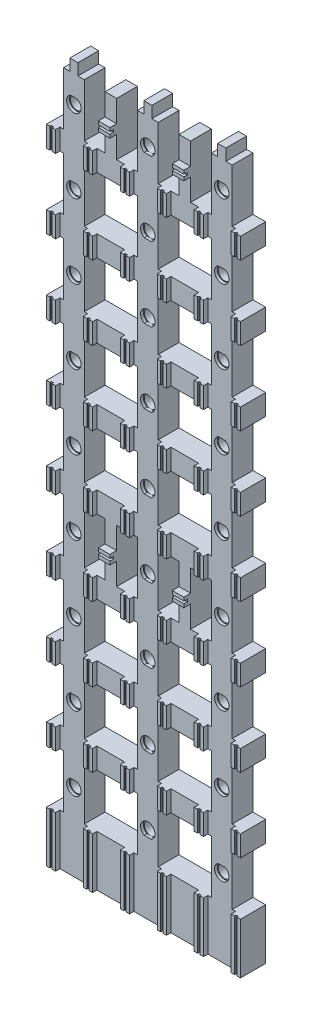
SolidWorks part; units mm, degrees
ref_plane "Front Plane" through (0, 0, 0) normal (0, 0, 1) x (1, 0, 0)
ref_plane "Top Plane" through (0, 0, 0) normal (0, 1, 0) x (1, 0, 0)
ref_plane "Right Plane" through (0, 0, 0) normal (1, 0, 0) x (0, 0, -1)
sketch "Sketch1" plane through (0, 0, 0) normal (0, 0, 1) x (1, 0, 0)
  line L1 (42, -11) -> (-42, -11)
  line L2 (42, -11) -> (42, 11)
  line L3 (42, 11) -> (-42, 11)
  line L4 (-42, -11) -> (-42, 11)
  line L5 (42, -11) -> (-42, 11) construction
  line L6 (42, 11) -> (-42, -11) construction
  point P0 (0, 0)
  dimension "D1" = 22
  dimension "D2" = 84
extrude "Boss-Extrude1" add sketch "Sketch1" along normal blind 9
sketch "Sketch2" plane through (0, 0, 9) normal (0, 0, 1) x (1, 0, 0)
  line L0 (42, 11) -> (-42, 11) construction
  line L1 (-36.5, 11) -> (-27.5, 11)
  line L2 (-36.5, 11) -> (-36.5, 295) construction
  line L3 (-36.5, 295) -> (-27.5, 295) construction
  line L4 (-27.5, 11) -> (-27.5, 295) construction
  line L5 (-42, 11) -> (-42, -11) construction
  line L6 (-33.75, 295) -> (-30.25, 295)
  line L7 (-30.25, 295) -> (-30.25, 290)
  line L8 (-30.25, 290) -> (-27.5, 290)
  line L9 (-27.5, 290) -> (-27.5, 11)
  line L10 (-36.5, 11) -> (-36.5, 290)
  line L11 (-36.5, 290) -> (-33.75, 290)
  line L12 (-33.75, 290) -> (-33.75, 295)
  point P10 (-32, 295)
  point P15 (-32, 11)
  dimension "D1" = 5.5
  dimension "D2" = 9
  dimension "D3" = 284
  dimension "D4" = 5
  dimension "D5" = 3.5
extrude "Boss-Extrude2" add sketch "Sketch2" against normal up to surface (9 mm away) up to face at (0, 0, 0)
pattern_linear "LPattern1" count 3 spacing 32 along (1, 0, 0) of "Boss-Extrude2"
sketch "Sketch3" plane through (0, 0, 9) normal (0, 0, 1) x (1, 0, 0)
  line L0 (-42, 11) -> (-42, -11) construction
  line L1 (-42, 43) -> (42, 43)
  line L2 (-42, 43) -> (-42, 34)
  line L3 (-42, 34) -> (42, 34)
  line L4 (42, 43) -> (42, 34)
  line L5 (42, -11) -> (42, 11) construction
  line L6 (-36.5, 11) -> (-42, 11) construction
  dimension "D1" = 23
  dimension "D2" = 9
extrude "Boss-Extrude3" add sketch "Sketch3" against normal up to surface (9 mm away) up to face at (0, 189.8571, 0)
pattern_linear "LPattern2" count 8 spacing 32 along (0, 1, 0) of "Boss-Extrude3"
sketch "Sketch4" plane through (0, 0, 9) normal (0, 0, 1) x (1, 0, 0)
  line L0 (-27.5, 130) -> (-4.5, 130) construction
  line L1 (-13.5, 130) -> (-18.5, 130)
  line L2 (-13.5, 130) -> (-13.5, 107)
  line L3 (-13.5, 107) -> (-18.5, 107)
  line L4 (-18.5, 130) -> (-18.5, 107)
  line L5 (-4.5, 107) -> (-27.5, 107) construction
  point P8 (-16, 107)
  dimension "D1" = 5
extrude "Boss-Extrude4" add sketch "Sketch4" against normal up to surface (9 mm away) up to face at (-16, 246.5, 0)
pattern_linear "LPattern3" count 2 spacing 32 along (1, 0, 0) count 2 spacing 160 along (0, 1, 0) of "Boss-Extrude4"
sketch "Sketch5" plane through (0, 0, 9) normal (0, 0, 1) x (1, 0, 0)
  line L0 (-36.5, 22.5) -> (-27.5, 22.5) construction
  line L1 (-36.5, 34) -> (-36.5, 11) construction
  line L2 (-27.5, 11) -> (-27.5, 34) construction
  line L3 (-4.5, 22.5) -> (4.5, 22.5) construction
  line L4 (-4.5, 34) -> (-4.5, 11) construction
  line L5 (4.5, 11) -> (4.5, 34) construction
  line L6 (27.5, 22.5) -> (36.5, 22.5) construction
  line L7 (27.5, 34) -> (27.5, 11) construction
  line L8 (36.5, 11) -> (36.5, 34) construction
  circle A0 centre (-32, 22.5) radius 2.725
  circle A1 centre (0, 22.5) radius 2.725
  circle A2 centre (32, 22.5) radius 2.725
  circle A3 centre (-32, 54.5) radius 2.725
  circle A4 centre (0, 54.5) radius 2.725
  circle A5 centre (32, 54.5) radius 2.725
  circle A6 centre (-32, 86.5) radius 2.725
  circle A7 centre (0, 86.5) radius 2.725
  circle A8 centre (32, 86.5) radius 2.725
  circle A9 centre (-32, 118.5) radius 2.725
  circle A10 centre (0, 118.5) radius 2.725
  circle A11 centre (32, 118.5) radius 2.725
  circle A12 centre (-32, 150.5) radius 2.725
  circle A13 centre (0, 150.5) radius 2.725
  circle A14 centre (32, 150.5) radius 2.725
  circle A15 centre (-32, 182.5) radius 2.725
  circle A16 centre (0, 182.5) radius 2.725
  circle A17 centre (32, 182.5) radius 2.725
  circle A18 centre (-32, 214.5) radius 2.725
  circle A19 centre (0, 214.5) radius 2.725
  circle A20 centre (32, 214.5) radius 2.725
  circle A21 centre (-32, 246.5) radius 2.725
  circle A22 centre (0, 246.5) radius 2.725
  circle A23 centre (32, 246.5) radius 2.725
  circle A24 centre (-32, 278.5) radius 2.725
  circle A25 centre (0, 278.5) radius 2.725
  circle A26 centre (32, 278.5) radius 2.725
  dimension "D1" = 5.45
  dimension "D3" = 32
  dimension "D2" = 9
extrude "Cut-Extrude1" cut sketch "Sketch5" against normal through all
sketch "Sketch6" plane through (0, 0, 9) normal (0, 0, 1) x (1, 0, 0)
  line L27 (-33.5297, 25.225) -> (-30.4703, 25.225)
  line L28 (-1.5297, 19.775) -> (1.5297, 19.775)
  line L29 (30.4703, 25.225) -> (33.5297, 25.225)
  line L30 (-33.5297, 57.225) -> (-30.4703, 57.225)
  line L31 (-1.5297, 51.775) -> (1.5297, 51.775)
  line L32 (30.4703, 57.225) -> (33.5297, 57.225)
  line L33 (-33.5297, 89.225) -> (-30.4703, 89.225)
  line L34 (-1.5297, 83.775) -> (1.5297, 83.775)
  line L35 (30.4703, 89.225) -> (33.5297, 89.225)
  line L36 (-33.5297, 121.225) -> (-30.4703, 121.225)
  line L37 (-1.5297, 115.775) -> (1.5297, 115.775)
  line L38 (30.4703, 121.225) -> (33.5297, 121.225)
  line L39 (-33.5297, 153.225) -> (-30.4703, 153.225)
  line L40 (-1.5297, 147.775) -> (1.5297, 147.775)
  line L41 (30.4703, 153.225) -> (33.5297, 153.225)
  line L42 (-33.5297, 185.225) -> (-30.4703, 185.225)
  line L43 (-1.5297, 179.775) -> (1.5297, 179.775)
  line L44 (30.4703, 185.225) -> (33.5297, 185.225)
  line L45 (-33.5297, 217.225) -> (-30.4703, 217.225)
  line L46 (-1.5297, 211.775) -> (1.5297, 211.775)
  line L47 (30.4703, 217.225) -> (33.5297, 217.225)
  line L48 (-33.5297, 249.225) -> (-30.4703, 249.225)
  line L49 (-1.5297, 243.775) -> (1.5297, 243.775)
  line L50 (30.4703, 249.225) -> (33.5297, 249.225)
  line L51 (-33.5297, 281.225) -> (-30.4703, 281.225)
  line L52 (-1.5297, 275.775) -> (1.5297, 275.775)
  line L53 (30.4703, 281.225) -> (33.5297, 281.225)
  arc A30 (-33.5297, 25.225) -> (-30.4703, 25.225) centre (-32, 22.5) ccw
  arc A31 (1.5297, 19.775) -> (-1.5297, 19.775) centre (0, 22.5) ccw
  arc A32 (30.4703, 25.225) -> (33.5297, 25.225) centre (32, 22.5) ccw
  circle A33 centre (32, 22.5) radius 2.725 construction
  circle A34 centre (0, 22.5) radius 2.725 construction
  circle A35 centre (-32, 22.5) radius 2.725 construction
  arc A36 (-33.5297, 57.225) -> (-30.4703, 57.225) centre (-32, 54.5) ccw
  arc A37 (1.5297, 51.775) -> (-1.5297, 51.775) centre (0, 54.5) ccw
  arc A38 (30.4703, 57.225) -> (33.5297, 57.225) centre (32, 54.5) ccw
  arc A39 (-33.5297, 89.225) -> (-30.4703, 89.225) centre (-32, 86.5) ccw
  arc A40 (1.5297, 83.775) -> (-1.5297, 83.775) centre (0, 86.5) ccw
  arc A41 (30.4703, 89.225) -> (33.5297, 89.225) centre (32, 86.5) ccw
  arc A42 (-33.5297, 121.225) -> (-30.4703, 121.225) centre (-32, 118.5) ccw
  arc A43 (1.5297, 115.775) -> (-1.5297, 115.775) centre (0, 118.5) ccw
  arc A44 (30.4703, 121.225) -> (33.5297, 121.225) centre (32, 118.5) ccw
  arc A45 (-33.5297, 153.225) -> (-30.4703, 153.225) centre (-32, 150.5) ccw
  arc A46 (1.5297, 147.775) -> (-1.5297, 147.775) centre (0, 150.5) ccw
  arc A47 (30.4703, 153.225) -> (33.5297, 153.225) centre (32, 150.5) ccw
  arc A48 (-33.5297, 185.225) -> (-30.4703, 185.225) centre (-32, 182.5) ccw
  arc A49 (1.5297, 179.775) -> (-1.5297, 179.775) centre (0, 182.5) ccw
  arc A50 (30.4703, 185.225) -> (33.5297, 185.225) centre (32, 182.5) ccw
  arc A51 (-33.5297, 217.225) -> (-30.4703, 217.225) centre (-32, 214.5) ccw
  arc A52 (1.5297, 211.775) -> (-1.5297, 211.775) centre (0, 214.5) ccw
  arc A53 (30.4703, 217.225) -> (33.5297, 217.225) centre (32, 214.5) ccw
  arc A54 (-33.5297, 249.225) -> (-30.4703, 249.225) centre (-32, 246.5) ccw
  arc A55 (1.5297, 243.775) -> (-1.5297, 243.775) centre (0, 246.5) ccw
  arc A56 (30.4703, 249.225) -> (33.5297, 249.225) centre (32, 246.5) ccw
  arc A57 (-33.5297, 281.225) -> (-30.4703, 281.225) centre (-32, 278.5) ccw
  arc A58 (1.5297, 275.775) -> (-1.5297, 275.775) centre (0, 278.5) ccw
  arc A59 (30.4703, 281.225) -> (33.5297, 281.225) centre (32, 278.5) ccw
  dimension "D1" = 6.25
  dimension "D2" = 32
extrude "Cut-Extrude2" cut sketch "Sketch6" against normal blind 1.2
sketch "Sketch7" plane through (0, 0, 9) normal (0, 0, 1) x (1, 0, 0)
  line L0 (-42, -11) -> (42, -11) construction
  line L1 (-42, 11) -> (-38, 11)
  line L2 (-42, 11) -> (-42, -11)
  line L3 (-42, -11) -> (-38, -11)
  line L4 (-38, 11) -> (-38, -11)
  line L5 (-36.5, 34) -> (-36.5, 11) construction
  line L11 (-26, 11) -> (-22, 11)
  line L12 (-26, 11) -> (-26, -11)
  line L13 (-26, -11) -> (-22, -11)
  line L14 (-22, 11) -> (-22, -11)
  line L15 (-10, 11) -> (-6, 11)
  line L16 (-10, 11) -> (-10, -11)
  line L17 (-10, -11) -> (-6, -11)
  line L18 (-6, 11) -> (-6, -11)
  line L19 (6, 11) -> (10, 11)
  line L20 (6, 11) -> (6, -11)
  line L21 (6, -11) -> (10, -11)
  line L22 (10, 11) -> (10, -11)
  line L23 (22, 11) -> (26, 11)
  line L24 (22, 11) -> (22, -11)
  line L25 (22, -11) -> (26, -11)
  line L26 (26, 11) -> (26, -11)
  line L27 (38, 11) -> (42, 11)
  line L28 (38, 11) -> (38, -11)
  line L29 (38, -11) -> (42, -11)
  line L30 (42, 11) -> (42, -11)
  dimension "D1" = 1.5
  dimension "D3" = 16
  dimension "D5" = 32
  dimension "D2" = 2
  dimension "D4" = 3
extrude "Boss-Extrude5" add sketch "Sketch7" along normal blind 1.9
sketch "Sketch8" plane through (0, 0, 9) normal (0, 0, 1) x (1, 0, 0)
  line L0 (-42, 34) -> (-36.5, 34) construction
  line L1 (-42, 43) -> (-38, 43)
  line L2 (-42, 43) -> (-42, 34)
  line L3 (-42, 34) -> (-38, 34)
  line L4 (-38, 43) -> (-38, 34)
  line L5 (-38, -11) -> (-38, 11) construction
  line L6 (-26, 43) -> (-22, 43)
  line L7 (-26, 43) -> (-26, 34)
  line L8 (-26, 34) -> (-22, 34)
  line L9 (-22, 43) -> (-22, 34)
  line L10 (-10, 43) -> (-6, 43)
  line L11 (-10, 43) -> (-10, 34)
  line L12 (-10, 34) -> (-6, 34)
  line L13 (-6, 43) -> (-6, 34)
  line L14 (6, 43) -> (10, 43)
  line L15 (6, 43) -> (6, 34)
  line L16 (6, 34) -> (10, 34)
  line L17 (10, 43) -> (10, 34)
  line L18 (22, 43) -> (26, 43)
  line L19 (22, 43) -> (22, 34)
  line L20 (22, 34) -> (26, 34)
  line L21 (26, 43) -> (26, 34)
  line L22 (38, 43) -> (42, 43)
  line L23 (38, 43) -> (38, 34)
  line L24 (38, 34) -> (42, 34)
  line L25 (42, 43) -> (42, 34)
  dimension "D2" = 16
  dimension "D4" = 32
  dimension "D1" = 2
  dimension "D3" = 3
extrude "Boss-Extrude6" add sketch "Sketch8" along normal up to surface (1.9 mm away) up to face at (-40, 0, 10.9)
pattern_linear "LPattern4" count 8 spacing 32 along (0, 1, 0) of "Boss-Extrude6"
sketch "Sketch9" plane through (0, 0, 10.9) normal (0, 0, 1) x (1, 0, 0)
  line L0 (-42, -11) -> (-38, -11) construction
  line L1 (-40.5, -11) -> (-39.5, -11)
  line L2 (-40.5, -11) -> (-40.5, 11)
  line L3 (-40.5, 11) -> (-39.5, 11)
  line L4 (-39.5, -11) -> (-39.5, 11)
  line L5 (-38, 11) -> (-42, 11) construction
  point P8 (-40, 11)
  dimension "D1" = 1
extrude "Cut-Extrude3" cut sketch "Sketch9" against normal blind 0.6
pattern_linear "LPattern5" count 6 spacing 16 along (1, 0, 0) count 9 spacing 32 along (0, 1, 0) of "Cut-Extrude3"
sketch "Sketch10" plane through (0, 0, 9) normal (0, 0, 1) x (1, 0, 0)
  line L0 (-18.5, 130) -> (-18.5, 107) construction
  line L1 (-18.5, 120.5) -> (-13.5, 120.5)
  line L2 (-18.5, 120.5) -> (-18.5, 116.5)
  line L3 (-18.5, 116.5) -> (-13.5, 116.5)
  line L4 (-13.5, 120.5) -> (-13.5, 116.5)
  line L5 (-13.5, 107) -> (-13.5, 130) construction
  point P8 (-18.5, 118.5)
  dimension "D1" = 4
extrude "Boss-Extrude7" add sketch "Sketch10" along normal blind 2.9
pattern_linear "LPattern6" count 2 spacing 32 along (1, 0, 0) count 2 spacing 160 along (0, 1, 0) of "Boss-Extrude7"
sketch "Sketch11" plane through (0, 0, 11.9) normal (0, 0, 1) x (1, 0, 0)
  line L0 (-18.5, 120.5) -> (-18.5, 116.5) construction
  line L1 (-18.5, 119) -> (-13.5, 119)
  line L2 (-18.5, 119) -> (-18.5, 118)
  line L3 (-18.5, 118) -> (-13.5, 118)
  line L4 (-13.5, 119) -> (-13.5, 118)
  line L5 (-13.5, 116.5) -> (-13.5, 120.5) construction
  point P8 (-18.5, 118.5)
  dimension "D1" = 1
extrude "Cut-Extrude4" cut sketch "Sketch11" against normal blind 1.5
pattern_linear "LPattern7" count 2 spacing 32 along (1, 0, 0) count 2 spacing 160 along (0, 1, 0) of "Cut-Extrude4"
